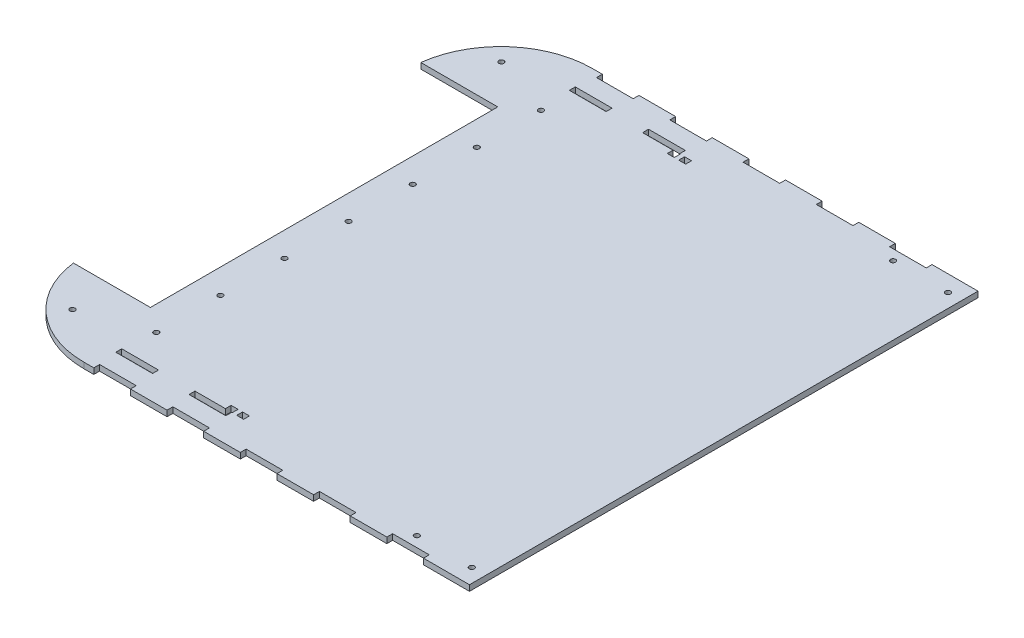
SolidWorks part; units mm, degrees
ref_plane "Front Plane" through (0, 0, 0) normal (0, 0, 1) x (1, 0, 0)
ref_plane "Top Plane" through (0, 0, 0) normal (0, 1, 0) x (1, 0, 0)
ref_plane "Right Plane" through (0, 0, 0) normal (1, 0, 0) x (0, 0, -1)
sketch "Sketch2" plane through (0, 0, 0) normal (0, 1, 0) x (1, 0, 0)
  line L0 (-157.5283, -142.1674) -> (-157.5283, 105.4826) construction
  line L1 (-157.5283, -142.1674) -> (-157.5283, 105.4826)
  line L2 (-125.7745, 107.0576) -> (-145.7745, 107.0576) construction
  line L3 (-199.5283, -108.1674) -> (-199.5283, 71.4826)
  line L4 (45.6717, 105.4826) -> (45.6717, -142.1674) construction
  line L5 (45.6717, 105.4826) -> (45.6717, -142.1674)
  line L6 (-145.7745, 107.0576) -> (-145.7745, 103.9076) construction
  line L7 (-145.7745, 103.9076) -> (-125.7745, 103.9076) construction
  line L8 (-125.7745, 103.9076) -> (-125.7745, 107.0576) construction
  line L9 (-85.7745, 107.0576) -> (-105.7745, 107.0576) construction
  line L10 (-199.5283, 71.4826) -> (-199.5283, 105.4826)
  line L11 (-199.5283, 105.4826) -> (-157.5283, 105.4826)
  line L12 (-199.5283, -108.1674) -> (-199.5283, -142.1674)
  line L13 (-199.5283, 120.4826) -> (-157.5283, 120.4826)
  line L14 (-157.5283, 120.4826) -> (60.6717, 120.4826)
  line L15 (60.6717, 120.4826) -> (60.6717, -157.1674)
  line L16 (60.6717, -157.1674) -> (-157.5283, -157.1674)
  line L17 (-157.5283, 107.4826) -> (45.6717, 107.4826)
  line L18 (45.6717, -144.1674) -> (-157.5283, -144.1674)
  line L19 (-157.5283, 105.4826) -> (-157.5283, 107.4826)
  line L20 (45.6717, 105.4826) -> (45.6717, 107.4826)
  line L21 (45.6717, -142.1674) -> (45.6717, -144.1674)
  line L22 (-157.5283, -142.1674) -> (-157.5283, -144.1674)
  line L23 (45.6717, 107.4826) -> (60.6717, 107.4826)
  line L24 (45.6717, -144.1674) -> (60.6717, -144.1674)
  line L25 (-157.5283, -157.1674) -> (-199.5283, -157.1674)
  line L26 (-199.5283, -157.1674) -> (-199.5283, -142.1674)
  line L27 (-199.5283, 120.4826) -> (-199.5283, 105.4826)
  line L28 (-105.7745, 107.0576) -> (-105.7745, 103.9076) construction
  line L29 (-105.7745, 103.9076) -> (-85.7745, 103.9076) construction
  line L30 (-85.7745, 103.9076) -> (-85.7745, 107.0576) construction
  line L31 (45.6717, -142.1674) -> (-157.5283, -142.1674) construction
  line L32 (-157.5283, 105.4826) -> (45.6717, 105.4826) construction
  line L33 (-125.7745, -140.5924) -> (-145.7745, -140.5924) construction
  line L34 (-162.1567, 71.4826) -> (-157.5283, 71.4826) construction
  line L35 (-194.8999, 71.4826) -> (-199.5283, 71.4826) construction
  line L36 (-162.1567, -108.1674) -> (-157.5283, -108.1674) construction
  line L37 (-199.5283, -108.1674) -> (-194.8999, -108.1674) construction
  line L38 (-162.1567, -108.1674) -> (-194.8999, -108.1674) construction
  line L39 (-194.8999, 71.4826) -> (-162.1567, 71.4826) construction
  line L40 (-145.7745, -140.5924) -> (-145.7745, -143.7424) construction
  line L41 (-145.7745, -143.7424) -> (-125.7745, -143.7424) construction
  line L42 (-125.7745, -143.7424) -> (-125.7745, -140.5924) construction
  line L43 (-199.5283, -113.1674) -> (-194.8999, -113.1674)
  line L44 (-162.1567, -113.1674) -> (-194.8999, -113.1674)
  line L45 (-162.1567, -113.1674) -> (-157.5283, -113.1674)
  line L46 (-194.8999, 76.4826) -> (-199.5283, 76.4826)
  line L47 (-194.8999, 76.4826) -> (-162.1567, 76.4826)
  line L48 (-162.1567, 76.4826) -> (-157.5283, 76.4826)
  line L49 (-85.7745, -140.5924) -> (-105.7745, -140.5924) construction
  line L50 (-105.7745, -140.5924) -> (-105.7745, -143.7424) construction
  line L51 (-105.7745, -143.7424) -> (-85.7745, -143.7424) construction
  line L52 (-85.7745, -143.7424) -> (-85.7745, -140.5924) construction
  line L53 (-125.7745, 107.0576) -> (-145.7745, 107.0576) construction
  line L54 (-145.7745, 107.0576) -> (-145.7745, 103.9076) construction
  line L55 (-145.7745, 103.9076) -> (-125.7745, 103.9076) construction
  line L56 (-125.7745, 103.9076) -> (-125.7745, 107.0576) construction
  line L57 (-85.7745, 107.0576) -> (-105.7745, 107.0576) construction
  line L58 (-105.7745, 107.0576) -> (-105.7745, 103.9076) construction
  line L59 (-105.7745, 103.9076) -> (-85.7745, 103.9076) construction
  line L60 (-85.7745, 103.9076) -> (-85.7745, 107.0576) construction
  line L61 (-125.7745, -140.5924) -> (-145.7745, -140.5924) construction
  line L62 (-145.7745, -140.5924) -> (-145.7745, -143.7424) construction
  line L63 (-145.7745, -143.7424) -> (-125.7745, -143.7424) construction
  line L64 (-125.7745, -143.7424) -> (-125.7745, -140.5924) construction
  line L65 (-85.7745, -140.5924) -> (-105.7745, -140.5924) construction
  line L66 (-105.7745, -140.5924) -> (-105.7745, -143.7424) construction
  line L67 (-105.7745, -143.7424) -> (-85.7745, -143.7424) construction
  line L68 (-85.7745, -143.7424) -> (-85.7745, -140.5924) construction
  line L69 (-125.7245, -140.5424) -> (-145.8245, -140.5424)
  line L70 (-145.8245, -140.5424) -> (-145.8245, -143.7924)
  line L71 (-145.8245, -143.7924) -> (-125.7245, -143.7924)
  line L72 (-125.7245, -143.7924) -> (-125.7245, -140.5424)
  line L73 (-85.7245, -140.5424) -> (-105.8245, -140.5424)
  line L74 (-105.8245, -140.5424) -> (-105.8245, -143.7924)
  line L75 (-105.8245, -143.7924) -> (-85.7245, -143.7924)
  line L76 (-85.7245, -143.7924) -> (-85.7245, -140.5424)
  line L77 (-145.8245, 103.8576) -> (-125.7245, 103.8576)
  line L78 (-125.7245, 103.8576) -> (-125.7245, 107.1076)
  line L79 (-125.7245, 107.1076) -> (-145.8245, 107.1076)
  line L80 (-145.8245, 107.1076) -> (-145.8245, 103.8576)
  line L81 (-105.8245, 103.8576) -> (-85.7245, 103.8576)
  line L82 (-85.7245, 103.8576) -> (-85.7245, 107.1076)
  line L83 (-85.7245, 107.1076) -> (-105.8245, 107.1076)
  line L84 (-105.8245, 107.1076) -> (-105.8245, 103.8576)
  dimension "D1" = 15
  dimension "D2" = 0.05
  dimension "D3" = 5
extrude "Boss-Extrude1" add sketch "Sketch2" along normal blind 3.15 contours L1 L22 L18 L21 L5 L20 L17 L19 | L47 L48 L1 L11 L10 L46 | L13 L27 L11 L19 L17 L23 L15 L14 | L21 L24 L15 L23 L20 L5 | L45 L44 L43 L12 L26 L25 L16 L15 L24 L18 L22 L1 region at (-99.7507, 0, 144.5529) region at (-55.6209, 0, 18.3424) region at (-178.5283, 0, -90.9826) region at (53.1717, 0, 18.3424) region at (-72.0719, 0, -113.8009)
fillet "Fillet1" radius 50 2 edges at (-199.5283, 1.575, -120.4826) (-199.5283, 1.575, 157.1674)
sketch "Sketch5" plane through (0, 0, 0) normal (0, 1, 0) x (1, 0, 0)
  line L0 (55.5717, 120.4826) -> (-144.4283, 120.4826) construction
  line L1 (-104.4283, 120.4826) -> (-84.4283, 120.4826)
  line L2 (-144.4283, 120.4826) -> (-124.4283, 120.4826)
  line L3 (-144.4283, 120.4826) -> (-144.4283, 117.3226)
  line L4 (-144.4283, 117.3226) -> (-124.4283, 117.3226)
  line L5 (-124.4283, 120.4826) -> (-124.4283, 117.3226)
  line L6 (-144.4283, 120.4826) -> (-124.4283, 117.3226) construction
  line L7 (-144.4283, 117.3226) -> (-124.4283, 120.4826) construction
  line L8 (-84.4283, 120.4826) -> (-84.4283, 117.3226)
  line L9 (-104.4283, 117.3226) -> (-84.4283, 117.3226)
  line L10 (-104.4283, 120.4826) -> (-104.4283, 117.3226)
  line L11 (-64.4283, 120.4826) -> (-44.4283, 120.4826)
  line L12 (-44.4283, 120.4826) -> (-44.4283, 117.3226)
  line L13 (-64.4283, 117.3226) -> (-44.4283, 117.3226)
  line L14 (-64.4283, 120.4826) -> (-64.4283, 117.3226)
  line L15 (-24.4283, 120.4826) -> (-4.4283, 120.4826)
  line L16 (-4.4283, 120.4826) -> (-4.4283, 117.3226)
  line L17 (-24.4283, 117.3226) -> (-4.4283, 117.3226)
  line L18 (-24.4283, 120.4826) -> (-24.4283, 117.3226)
  line L19 (15.5717, 120.4826) -> (35.5717, 120.4826)
  line L20 (35.5717, 120.4826) -> (35.5717, 117.3226)
  line L21 (15.5717, 117.3226) -> (35.5717, 117.3226)
  line L22 (15.5717, 120.4826) -> (15.5717, 117.3226)
  line L23 (-199.5283, -18.3424) -> (55.5717, -18.3424) construction
  line L25 (15.5717, -157.1674) -> (15.5717, -154.0074)
  line L26 (-24.4283, -157.1674) -> (-24.4283, -154.0074)
  line L27 (-64.4283, -157.1674) -> (-64.4283, -154.0074)
  line L28 (-104.4283, -157.1674) -> (-104.4283, -154.0074)
  line L29 (-144.4283, -154.0074) -> (-124.4283, -157.1674) construction
  line L30 (-144.4283, -157.1674) -> (-124.4283, -154.0074) construction
  line L31 (-144.4283, -157.1674) -> (-144.4283, -154.0074)
  line L32 (55.5717, -157.1674) -> (-144.4283, -157.1674) construction
  line L33 (15.5717, -154.0074) -> (35.5717, -154.0074)
  line L34 (35.5717, -157.1674) -> (35.5717, -154.0074)
  line L35 (15.5717, -157.1674) -> (35.5717, -157.1674)
  line L36 (-24.4283, -154.0074) -> (-4.4283, -154.0074)
  line L37 (-4.4283, -157.1674) -> (-4.4283, -154.0074)
  line L38 (-24.4283, -157.1674) -> (-4.4283, -157.1674)
  line L39 (-64.4283, -154.0074) -> (-44.4283, -154.0074)
  line L40 (-44.4283, -157.1674) -> (-44.4283, -154.0074)
  line L41 (-64.4283, -157.1674) -> (-44.4283, -157.1674)
  line L42 (-104.4283, -154.0074) -> (-84.4283, -154.0074)
  line L43 (-84.4283, -157.1674) -> (-84.4283, -154.0074)
  line L44 (-124.4283, -157.1674) -> (-124.4283, -154.0074)
  line L45 (-144.4283, -154.0074) -> (-124.4283, -154.0074)
  line L46 (-144.4283, -157.1674) -> (-124.4283, -157.1674)
  line L47 (-104.4283, -157.1674) -> (-84.4283, -157.1674)
  point P7 (-134.4283, 118.9026)
  point P49 (-134.4283, -155.5874)
  dimension "D1" = 20
  dimension "D2" = 3.16
  dimension "D3" = 5
extrude "Cut-Extrude2" cut sketch "Sketch5" along normal through all
sketch "Sketch7" plane through (0, 0, 0) normal (0, -1, 0) x (1, 0, 0)
  line L0 (60.6717, 18.3424) -> (19.0261, 18.3424) construction
  line L1 (60.6717, -120.4826) -> (60.6717, 157.1674) construction
  circle A0 centre (23.1217, 148.3424) radius 1.4 construction
  circle A1 centre (53.1217, 148.3424) radius 1.4 construction
  circle A2 centre (23.1217, 148.3424) radius 1.4
  circle A3 centre (53.1217, 148.3424) radius 1.4
  circle A4 centre (53.1217, -111.6576) radius 1.4
  circle A5 centre (23.1217, -111.6576) radius 1.4
extrude "Cut-Extrude3" cut sketch "Sketch7" against normal through all
sketch "Sketch8" plane through (0, 0, 0) normal (0, -1, 0) x (1, 0, 0)
  circle A1 centre (-177.8126, 135.4517) radius 1.4
  circle A2 centre (-177.8126, 135.4517) radius 1.4
  circle A3 centre (-177.8126, -98.7669) radius 1.4
  circle A4 centre (-177.8126, -98.7669) radius 1.4
  dimension "D1" = 0
  dimension "D2" = 0
extrude "Cut-Extrude4" cut sketch "Sketch8" against normal blind 10
sketch "Sketch10" plane through (0, 3.15, 0) normal (0, 1, 0) x (1, 0, 0)
  circle A0 centre (-144.1298, -123.3424) radius 1.4 construction
  circle A1 centre (-144.1298, 86.6576) radius 1.4 construction
  circle A2 centre (-144.1298, 51.6576) radius 1.4 construction
  circle A3 centre (-144.1298, 16.6576) radius 1.4 construction
  circle A4 centre (-144.1298, -18.3424) radius 1.4 construction
  circle A5 centre (-144.1298, -53.3424) radius 1.4 construction
  circle A6 centre (-144.1298, -88.3424) radius 1.4 construction
  circle A7 centre (-144.1298, -123.3424) radius 1.4
  circle A8 centre (-144.1298, 86.6576) radius 1.4
  circle A9 centre (-144.1298, 51.6576) radius 1.4
  circle A10 centre (-144.1298, 16.6576) radius 1.4
  circle A11 centre (-144.1298, -18.3424) radius 1.4
  circle A12 centre (-144.1298, -53.3424) radius 1.4
  circle A13 centre (-144.1298, -88.3424) radius 1.4
extrude "Cut-Extrude5" cut sketch "Sketch10" against normal blind 10
sketch "Sketch9" plane through (0, 3.15, 0) normal (0, 1, 0) x (1, 0, 0)
  line L46 (-84.4283, 117.3226) -> (-104.4283, 117.3226)
  line L47 (-104.4283, 117.3226) -> (-104.4283, 120.4826)
  line L48 (-104.4283, 120.4826) -> (-124.4283, 120.4826)
  line L49 (-124.4283, 120.4826) -> (-124.4283, 117.3226)
  line L50 (-124.4283, 117.3226) -> (-144.4283, 117.3226)
  line L51 (-144.4283, 117.3226) -> (-144.4283, 120.4826)
  line L52 (-144.4283, 120.4826) -> (-149.8896, 120.4826)
  line L53 (-199.5283, 76.4826) -> (-157.5283, 76.4826)
  line L54 (-157.5283, 76.4826) -> (-157.5283, -113.1674)
  line L55 (-157.5283, -113.1674) -> (-199.5283, -113.1674)
  line L56 (-149.8896, -157.1674) -> (-144.4283, -157.1674)
  line L57 (-144.4283, -157.1674) -> (-144.4283, -154.0074)
  line L58 (-144.4283, -154.0074) -> (-124.4283, -154.0074)
  line L59 (-124.4283, -154.0074) -> (-124.4283, -157.1674)
  line L60 (-124.4283, -157.1674) -> (-104.4283, -157.1674)
  line L61 (-104.4283, -157.1674) -> (-104.4283, -154.0074)
  line L62 (-104.4283, -154.0074) -> (-84.4283, -154.0074)
  line L63 (-84.4283, -154.0074) -> (-84.4283, -157.1674)
  line L64 (-84.4283, -157.1674) -> (-64.4283, -157.1674)
  line L65 (-64.4283, -157.1674) -> (-64.4283, -154.0074)
  line L66 (-64.4283, -154.0074) -> (-44.4283, -154.0074)
  line L67 (-44.4283, -154.0074) -> (-44.4283, -157.1674)
  line L68 (-44.4283, -157.1674) -> (-24.4283, -157.1674)
  line L69 (-24.4283, -157.1674) -> (-24.4283, -154.0074)
  line L70 (-24.4283, -154.0074) -> (-4.4283, -154.0074)
  line L71 (-4.4283, -154.0074) -> (-4.4283, -157.1674)
  line L72 (-4.4283, -157.1674) -> (15.5717, -157.1674)
  line L73 (15.5717, -157.1674) -> (15.5717, -154.0074)
  line L74 (15.5717, -154.0074) -> (35.5717, -154.0074)
  line L75 (35.5717, -154.0074) -> (35.5717, -157.1674)
  line L76 (35.5717, -157.1674) -> (60.6717, -157.1674)
  line L77 (60.6717, -157.1674) -> (60.6717, 120.4826)
  line L78 (60.6717, 120.4826) -> (35.5717, 120.4826)
  line L79 (35.5717, 120.4826) -> (35.5717, 117.3226)
  line L80 (35.5717, 117.3226) -> (15.5717, 117.3226)
  line L81 (15.5717, 117.3226) -> (15.5717, 120.4826)
  line L82 (15.5717, 120.4826) -> (-4.4283, 120.4826)
  line L83 (-4.4283, 120.4826) -> (-4.4283, 117.3226)
  line L84 (-4.4283, 117.3226) -> (-24.4283, 117.3226)
  line L85 (-24.4283, 117.3226) -> (-24.4283, 120.4826)
  line L86 (-24.4283, 120.4826) -> (-44.4283, 120.4826)
  line L87 (-44.4283, 120.4826) -> (-44.4283, 117.3226)
  line L88 (-44.4283, 117.3226) -> (-64.4283, 117.3226)
  line L89 (-64.4283, 117.3226) -> (-64.4283, 120.4826)
  line L90 (-64.4283, 120.4826) -> (-84.4283, 120.4826)
  line L91 (-84.4283, 120.4826) -> (-84.4283, 117.3226)
  line L92 (-84.4283, 117.3226) -> (-104.4283, 117.3226)
  line L93 (-104.4283, 117.3226) -> (-104.4283, 120.4826)
  line L94 (-104.4283, 120.4826) -> (-124.4283, 120.4826)
  line L95 (-124.4283, 120.4826) -> (-124.4283, 117.3226)
  line L96 (-124.4283, 117.3226) -> (-144.4283, 117.3226)
  line L97 (-144.4283, 117.3226) -> (-144.4283, 120.4826)
  line L98 (-144.4283, 120.4826) -> (-149.8896, 120.4826)
  line L99 (-199.5283, 76.4826) -> (-157.5283, 76.4826)
  line L100 (-157.5283, 76.4826) -> (-157.5283, -113.1674)
  line L101 (-157.5283, -113.1674) -> (-199.5283, -113.1674)
  line L102 (-149.8896, -157.1674) -> (-144.4283, -157.1674)
  line L103 (-144.4283, -157.1674) -> (-144.4283, -154.0074)
  line L104 (-144.4283, -154.0074) -> (-124.4283, -154.0074)
  line L105 (-124.4283, -154.0074) -> (-124.4283, -157.1674)
  line L106 (-124.4283, -157.1674) -> (-104.4283, -157.1674)
  line L107 (-104.4283, -157.1674) -> (-104.4283, -154.0074)
  line L108 (-104.4283, -154.0074) -> (-84.4283, -154.0074)
  line L109 (-84.4283, -154.0074) -> (-84.4283, -157.1674)
  line L110 (-84.4283, -157.1674) -> (-64.4283, -157.1674)
  line L111 (-64.4283, -157.1674) -> (-64.4283, -154.0074)
  line L112 (-64.4283, -154.0074) -> (-44.4283, -154.0074)
  line L113 (-44.4283, -154.0074) -> (-44.4283, -157.1674)
  line L114 (-44.4283, -157.1674) -> (-24.4283, -157.1674)
  line L115 (-24.4283, -157.1674) -> (-24.4283, -154.0074)
  line L116 (-24.4283, -154.0074) -> (-4.4283, -154.0074)
  line L117 (-4.4283, -154.0074) -> (-4.4283, -157.1674)
  line L118 (-4.4283, -157.1674) -> (15.5717, -157.1674)
  line L119 (15.5717, -157.1674) -> (15.5717, -154.0074)
  line L120 (15.5717, -154.0074) -> (35.5717, -154.0074)
  line L121 (35.5717, -154.0074) -> (35.5717, -157.1674)
  line L122 (35.5717, -157.1674) -> (60.6717, -157.1674)
  line L123 (60.6717, -157.1674) -> (60.6717, 120.4826)
  line L124 (60.6717, 120.4826) -> (35.5717, 120.4826)
  line L125 (35.5717, 120.4826) -> (35.5717, 117.3226)
  line L126 (35.5717, 117.3226) -> (15.5717, 117.3226)
  line L127 (15.5717, 117.3226) -> (15.5717, 120.4826)
  line L128 (15.5717, 120.4826) -> (-4.4283, 120.4826)
  line L129 (-4.4283, 120.4826) -> (-4.4283, 117.3226)
  line L130 (-4.4283, 117.3226) -> (-24.4283, 117.3226)
  line L131 (-24.4283, 117.3226) -> (-24.4283, 120.4826)
  line L132 (-24.4283, 120.4826) -> (-44.4283, 120.4826)
  line L133 (-44.4283, 120.4826) -> (-44.4283, 117.3226)
  line L134 (-44.4283, 117.3226) -> (-64.4283, 117.3226)
  line L135 (-64.4283, 117.3226) -> (-64.4283, 120.4826)
  line L136 (-64.4283, 120.4826) -> (-84.4283, 120.4826)
  line L137 (-84.4283, 120.4826) -> (-84.4283, 117.3226)
  line L142 (-125.7245, -143.7924) -> (-125.7245, -140.5424)
  line L143 (-145.8245, -143.7924) -> (-125.7245, -143.7924)
  line L144 (-145.8245, -140.5424) -> (-145.8245, -143.7924)
  line L145 (-125.7245, -140.5424) -> (-145.8245, -140.5424)
  line L146 (-125.7245, -143.7924) -> (-125.7245, -140.5424)
  line L147 (-145.8245, -143.7924) -> (-125.7245, -143.7924)
  line L148 (-145.8245, -140.5424) -> (-145.8245, -143.7924)
  line L149 (-125.7245, -140.5424) -> (-145.8245, -140.5424)
  line L150 (-85.7245, -143.7924) -> (-85.7245, -140.5424)
  line L151 (-105.8245, -143.7924) -> (-85.7245, -143.7924)
  line L152 (-105.8245, -140.5424) -> (-105.8245, -143.7924)
  line L153 (-85.7245, -140.5424) -> (-105.8245, -140.5424)
  line L154 (-85.7245, -143.7924) -> (-85.7245, -140.5424)
  line L155 (-105.8245, -143.7924) -> (-85.7245, -143.7924)
  line L156 (-105.8245, -140.5424) -> (-105.8245, -143.7924)
  line L157 (-85.7245, -140.5424) -> (-105.8245, -140.5424)
  line L158 (-145.8245, 107.1076) -> (-145.8245, 103.8576)
  line L159 (-125.7245, 107.1076) -> (-145.8245, 107.1076)
  line L160 (-125.7245, 103.8576) -> (-125.7245, 107.1076)
  line L161 (-145.8245, 103.8576) -> (-125.7245, 103.8576)
  line L162 (-145.8245, 107.1076) -> (-145.8245, 103.8576)
  line L163 (-125.7245, 107.1076) -> (-145.8245, 107.1076)
  line L164 (-125.7245, 103.8576) -> (-125.7245, 107.1076)
  line L165 (-145.8245, 103.8576) -> (-125.7245, 103.8576)
  line L166 (-105.8245, 107.1076) -> (-105.8245, 103.8576)
  line L167 (-85.7245, 107.1076) -> (-105.8245, 107.1076)
  line L168 (-85.7245, 103.8576) -> (-85.7245, 107.1076)
  line L169 (-105.8245, 103.8576) -> (-85.7245, 103.8576)
  line L170 (-105.8245, 107.1076) -> (-105.8245, 103.8576)
  line L171 (-85.7245, 107.1076) -> (-105.8245, 107.1076)
  line L172 (-85.7245, 103.8576) -> (-85.7245, 107.1076)
  line L173 (-105.8245, 103.8576) -> (-85.7245, 103.8576)
  arc A2 (-149.8896, 120.4826) -> (-199.5283, 76.4826) centre (-149.8896, 70.4826) ccw
  arc A3 (-199.5283, -113.1674) -> (-149.8896, -157.1674) centre (-149.8896, -107.1674) ccw
  arc A4 (-149.8896, 120.4826) -> (-199.5283, 76.4826) centre (-149.8896, 70.4826) ccw
  arc A5 (-199.5283, -113.1674) -> (-149.8896, -157.1674) centre (-149.8896, -107.1674) ccw
  circle A7 centre (23.1217, -148.3424) radius 1.4
  circle A8 centre (23.1217, -148.3424) radius 1.4
  circle A9 centre (23.1217, 111.6576) radius 1.4
  circle A10 centre (23.1217, 111.6576) radius 1.4
  circle A11 centre (53.1217, 111.6576) radius 1.4
  circle A12 centre (53.1217, 111.6576) radius 1.4
  circle A13 centre (53.1217, -148.3424) radius 1.4
  circle A14 centre (53.1217, -148.3424) radius 1.4
  circle A15 centre (-177.8126, -135.4517) radius 1.4
  circle A16 centre (-177.8126, -135.4517) radius 1.4
  circle A17 centre (-177.8126, 98.7669) radius 1.4
  circle A18 centre (-177.8126, 98.7669) radius 1.4
  circle A19 centre (-144.1298, 86.6576) radius 1.4
  circle A20 centre (-144.1298, 86.6576) radius 1.4
  circle A21 centre (-144.1298, 51.6576) radius 1.4
  circle A22 centre (-144.1298, 51.6576) radius 1.4
  circle A23 centre (-144.1298, 16.6576) radius 1.4
  circle A24 centre (-144.1298, 16.6576) radius 1.4
  circle A25 centre (-144.1298, -18.3424) radius 1.4
  circle A26 centre (-144.1298, -18.3424) radius 1.4
  circle A27 centre (-144.1298, -53.3424) radius 1.4
  circle A28 centre (-144.1298, -53.3424) radius 1.4
  circle A29 centre (-144.1298, -88.3424) radius 1.4
  circle A30 centre (-144.1298, -88.3424) radius 1.4
  circle A31 centre (-144.1298, -123.3424) radius 1.4
  circle A32 centre (-144.1298, -123.3424) radius 1.4
  dimension "D1" = 0
  dimension "D2" = 0
  dimension "D3" = 0
  dimension "D4" = 0
  dimension "D5" = 0
  dimension "D6" = 0
  dimension "D7" = 0
  dimension "D8" = 0
  dimension "D9" = 0
  dimension "D10" = 0
  dimension "D11" = 0
  dimension "D12" = 0
  dimension "D13" = 0
  dimension "D14" = 0
  dimension "D15" = 0
  dimension "D16" = 0
  dimension "D17" = 0
  dimension "D18" = 0
sketch "Sketch11" plane through (0, 0, 0) normal (0, -1, 0) x (1, 0, 0)
  line L0 (-79.1949, 137.4424) -> (-82.9449, 137.4424) construction
  line L1 (-82.9449, 137.4424) -> (-82.9449, 140.5924) construction
  line L2 (-82.9449, 140.5924) -> (-79.1949, 140.5924) construction
  line L3 (-79.1949, 140.5924) -> (-79.1949, 137.4424) construction
  line L4 (-85.4449, 137.4424) -> (-89.1949, 137.4424) construction
  line L5 (-89.1949, 137.4424) -> (-89.1949, 140.5924) construction
  line L6 (-89.1949, 140.5924) -> (-85.4449, 140.5924) construction
  line L7 (-85.4449, 140.5924) -> (-85.4449, 137.4424) construction
  line L8 (-79.1949, 137.4424) -> (-82.9449, 137.4424) construction
  line L9 (-82.9449, 137.4424) -> (-82.9449, 140.5924) construction
  line L10 (-82.9449, 140.5924) -> (-79.1949, 140.5924) construction
  line L11 (-79.1949, 140.5924) -> (-79.1949, 137.4424) construction
  line L12 (-85.4449, 137.4424) -> (-89.1949, 137.4424) construction
  line L13 (-89.1949, 137.4424) -> (-89.1949, 140.5924) construction
  line L14 (-89.1949, 140.5924) -> (-85.4449, 140.5924) construction
  line L15 (-85.4449, 140.5924) -> (-85.4449, 137.4424) construction
  line L16 (-85.4449, -103.9076) -> (-89.1949, -103.9076) construction
  line L17 (-89.1949, -103.9076) -> (-89.1949, -100.7576) construction
  line L18 (-89.1949, -100.7576) -> (-85.4449, -100.7576) construction
  line L19 (-85.4449, -100.7576) -> (-85.4449, -103.9076) construction
  line L20 (-79.1949, -103.9076) -> (-82.9449, -103.9076) construction
  line L21 (-82.9449, -103.9076) -> (-82.9449, -100.7576) construction
  line L22 (-82.9449, -100.7576) -> (-79.1949, -100.7576) construction
  line L23 (-79.1949, -100.7576) -> (-79.1949, -103.9076) construction
  line L24 (-85.4449, -103.9076) -> (-89.1949, -103.9076) construction
  line L25 (-89.1949, -103.9076) -> (-89.1949, -100.7576) construction
  line L26 (-89.1949, -100.7576) -> (-85.4449, -100.7576) construction
  line L27 (-85.4449, -100.7576) -> (-85.4449, -103.9076) construction
  line L28 (-79.1949, -103.9076) -> (-82.9449, -103.9076) construction
  line L29 (-82.9449, -103.9076) -> (-82.9449, -100.7576) construction
  line L30 (-82.9449, -100.7576) -> (-79.1949, -100.7576) construction
  line L31 (-79.1949, -100.7576) -> (-79.1949, -103.9076) construction
  line L32 (-85.4249, -103.9276) -> (-89.2149, -103.9276)
  line L33 (-89.2149, -103.9276) -> (-89.2149, -100.7376)
  line L34 (-89.2149, -100.7376) -> (-85.4249, -100.7376)
  line L35 (-85.4249, -100.7376) -> (-85.4249, -103.9276)
  line L36 (-79.1749, -103.9276) -> (-82.9649, -103.9276)
  line L37 (-82.9649, -103.9276) -> (-82.9649, -100.7376)
  line L38 (-82.9649, -100.7376) -> (-79.1749, -100.7376)
  line L39 (-79.1749, -100.7376) -> (-79.1749, -103.9276)
  line L40 (-85.4249, 140.6124) -> (-85.4249, 137.4224)
  line L41 (-85.4249, 137.4224) -> (-89.2149, 137.4224)
  line L42 (-89.2149, 137.4224) -> (-89.2149, 140.6124)
  line L43 (-89.2149, 140.6124) -> (-85.4249, 140.6124)
  line L44 (-82.9649, 137.4224) -> (-82.9649, 140.6124)
  line L45 (-82.9649, 140.6124) -> (-79.1749, 140.6124)
  line L46 (-79.1749, 140.6124) -> (-79.1749, 137.4224)
  line L47 (-79.1749, 137.4224) -> (-82.9649, 137.4224)
  dimension "D1" = 0.02
extrude "Cut-Extrude6" cut sketch "Sketch11" against normal blind 10
